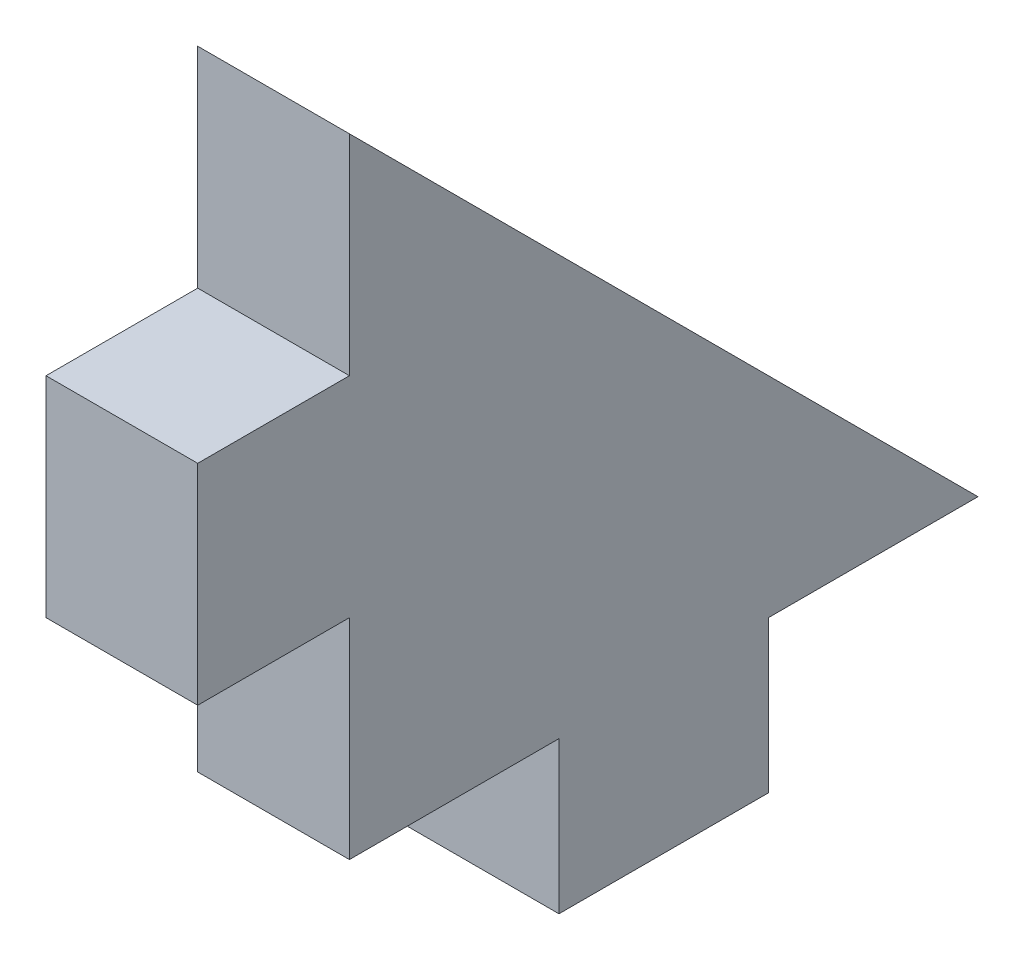
SolidWorks part; units mm, degrees
ref_plane "Front Plane" through (0, 0, 0) normal (0, 0, 1) x (1, 0, 0)
ref_plane "Top Plane" through (0, 0, 0) normal (0, 1, 0) x (1, 0, 0)
ref_plane "Right Plane" through (0, 0, 0) normal (1, 0, 0) x (0, 0, -1)
sketch "Sketch1" plane through (0, 0, 0) normal (1, 0, 0) x (0, 0, -1)
  line L0 (0, 21.2132) -> (21.2132, 0)
  line L1 (0, 0) -> (7.0711, 0)
  line L2 (0, 0) -> (0, 7.0711)
  line L3 (0, 14.1421) -> (0, 21.2132)
  line L4 (0, 14.1421) -> (-5.12, 14.1421)
  line L5 (14.1421, 0) -> (21.2132, 0)
  line L6 (0, 7.0711) -> (-5.12, 7.0711)
  line L7 (-5.12, 14.1421) -> (-5.12, 7.0711)
  line L9 (7.0711, 0) -> (7.0711, -5.12)
  line L10 (7.0711, -5.12) -> (14.1421, -5.12)
  line L11 (14.1421, 0) -> (14.1421, -5.12)
  dimension "D1" = 5.12
  dimension "D2" = 30
extrude "Boss-Extrude1" add sketch "Sketch1" along normal blind 5.12
equation "\"mdf\"=\"mdf@fmv1.assembly\""
equation "\"D1@Sketch1\"=\"mdf\""
equation "\"D1@Boss-Extrude1\"=\"mdf\""
